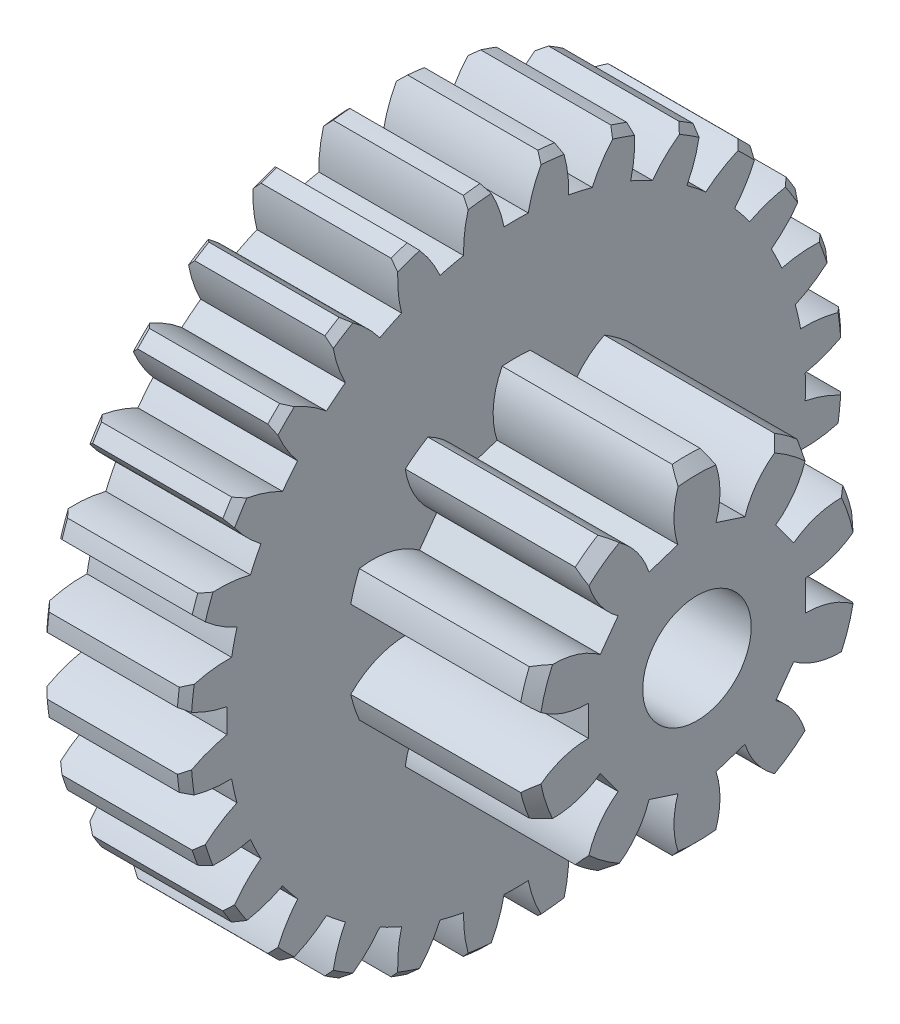
SolidWorks part; units mm, degrees
ref_plane "Plane1" through (0, 0, 0) normal (0, 0, 1) x (1, 0, 0)
ref_plane "Plane2" through (0, 0, 0) normal (0, 1, 0) x (1, 0, 0)
ref_plane "Plane3" through (0, 0, 0) normal (1, 0, 0) x (0, 0, -1)
sketch "BasProSke" plane through (0, 0, 0) normal (0, 1, 0) x (1, 0, 0)
  line L0 (-10, 0) -> (60, 0) construction
  line L1 (0, 0) -> (0, 9.2)
  line L2 (0, 0) -> (4, 0)
  line L3 (4, 0) -> (4, 9.2)
  line L4 (4, 9.2) -> (0, 9.2)
  dimension "Diameter" = 18.4
  dimension "Thickness" = 4
revolve "Base-Revolve" add sketch "BasProSke" angle 360 about L0
chamfer "倒角1" distance 0.2 angle 45 2 edges at (4, 0, 9.2) (0, 0, 9.2)
sketch "TooCutSke" plane through (0, 0, 0) normal (1, 0, 0) x (0, 0, -1)
  line L1 (0, 0) -> (0, 107) construction
  line L3 (0, 0) -> (-1.9561, 17.3613) construction
  arc A0 (0.3339, 7.993) -> (-0.3339, 7.993) centre (0, 0) ccw
  arc A1 (0.9784, 9.4248) -> (-0.9784, 9.4248) centre (0, 0) ccw
  circle A2 centre (0, 0) radius 8.75 construction
  circle A3 centre (0, 0) radius 8.2223 construction
  arc A4 (-0.3339, 7.993) -> (-0.9784, 9.4248) centre (-3.7664, 7.3089) ccw
  arc A5 (0.9784, 9.4248) -> (0.3339, 7.993) centre (3.7664, 7.3089) ccw
  dimension "Root_dia" = 16
  dimension "Overcut_dia" = 18.9508
  dimension "Pitch_dia" = 17.5
  dimension "Base_dia" = 16.4446
  dimension "Flank_rad" = 3.5
  dimension "Half_ang" = 6.429
extrude "ToothCut" cut sketch "TooCutSke" along normal through all
pattern_circular "TeethCuts" count 28 every 12.857 about axis through (-10, 0, 0) along (1, 0, 0) of "ToothCut"
ref_plane "FarPln" through (5, 0, 0) normal (1, 0, 0) x (0, 0, -1)
sketch "草图1" plane through (4, 0, 0) normal (1, 0, 0) x (0, 0, -1)
  circle A0 centre (0, 0) radius 4.7
  dimension "D1" = 9.4
extrude "凸台-拉伸1" add sketch "草图1" along normal blind 5
chamfer "倒角2" distance 0.3 angle 45 1 edges at (9, 0, -4.7)
sketch "草图2" plane through (9, 0, 0) normal (1, 0, 0) x (0, 0, -1)
  line L0 (0, 0) -> (10.6634, 0) construction
  line L1 (0, 0) -> (4.0504, -0.6852) construction
  line L2 (0, 0) -> (5.5893, -1.8161) construction
  line L3 (3, 0.4197) -> (3, -0.4197)
  line L4 (4.8461, -1.4205) -> (4.8461, 1.4205)
  arc A0 (3, -0.4197) -> (4.8461, -1.4205) centre (3.0036, -2.6161) cw
  circle A1 centre (0, 0) radius 5.05 construction
  circle A2 centre (0, 0) radius 3 construction
  arc A4 (3, 0.4197) -> (4.8461, 1.4205) centre (3.0036, 2.6161) ccw
  dimension "D3" = 10.1
  dimension "D5" = 6
  dimension "D1" = 0.6
  dimension "D2" = 18
extrude "切除-拉伸1" cut sketch "草图2" against normal up to surface (5 mm away) up to face at (4, 0, 0)
ref_axis "基准轴1" through (0, 0, 0) along (1, 0, 0)
pattern_circular "阵列(圆周)1" count 10 every 36 about axis through (0, 0, 0) along (1, 0, 0) of "切除-拉伸1"
sketch "草图3" plane through (9, 0, 0) normal (1, 0, 0) x (0, 0, -1)
  circle A0 centre (0, 0) radius 1.5
  dimension "D1" = 3
extrude "切除-拉伸2" cut sketch "草图3" against normal through all
sketch "草图4" plane through (0, 0, 0) normal (-1, 0, 0) x (0, 0, 1)
  circle A0 centre (0, 0) radius 5.5
  dimension "D1" = 11
extrude "切除-拉伸3" cut sketch "草图4" against normal blind 2
equation "' \"Module@HoldingSke\" = 6.35"
equation "' \"Num_teeth@HoldingSke\" = 12"
equation "' \"Ap@HoldingSke\" =  20"
equation "' \"Width@HoldingSke\" = 0.5 * 25.4"
equation "' \"Hub_dia@HoldingSke\"= 1 * 25.4"
equation "' \"Overall_len@HoldingSke\" = 1.0 * 25.4"
equation "' \"Bore@HoldingSke\" = 0.75 * 25.4"
equation "' \"T_dim@HoldingSke\" = 0.1 * 25.4"
equation "' \"Width@KeySke\" = 0.25 * 25.4"
equation "' \"Show_teeth@HoldingSke\" = 13"
equation "' \"Backlash@HoldingSke\" = 0.009 * 25.4"
equation "' \"Addendum_fac@HoldingSke\" = 1.0"
equation "' \"Dedendum_fac@HoldingSke\" = 1.25"
equation "' \"Dedendum_add@HoldingSke\" = 0.00005 * 25.4"
equation "' \"Clearance_fac@HoldingSke\" = 0.25"
equation "' \"Fillet_rad@BasProSke\" =  \"Thickness@HoldingSke\" * 0.05"
